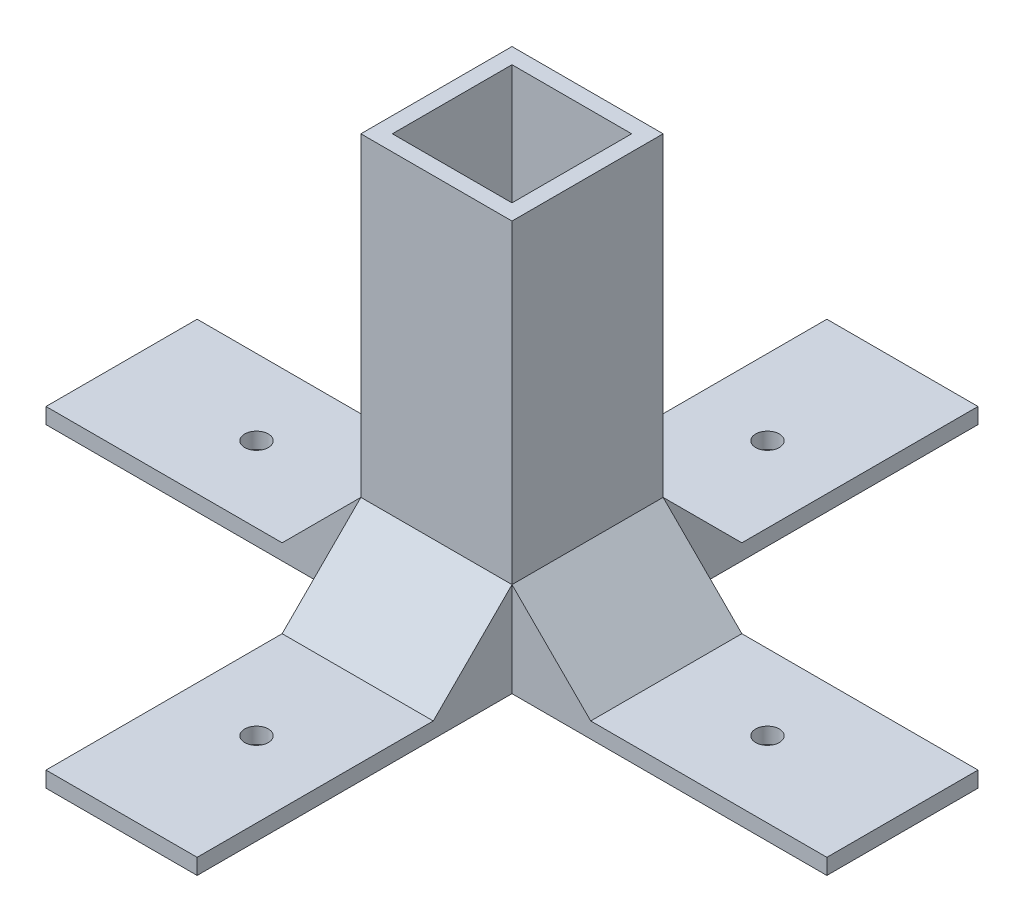
SolidWorks part; units mm, degrees
material "ABS"
ref_plane "Front Plane" through (0, 0, 0) normal (0, 0, 1) x (1, 0, 0)
ref_plane "Top Plane" through (0, 0, 0) normal (0, 1, 0) x (1, 0, 0)
ref_plane "Right Plane" through (0, 0, 0) normal (1, 0, 0) x (0, 0, -1)
sketch "Sketch1" plane through (0, 0, 0) normal (0, 1, 0) x (1, 0, 0)
  line L1 (-7.6, 7.6) -> (7.6, 7.6)
  line L2 (-7.6, 7.6) -> (-7.6, -7.6)
  line L3 (-7.6, -7.6) -> (7.6, -7.6)
  line L4 (7.6, 7.6) -> (7.6, -7.6)
  line L5 (-7.6, 7.6) -> (7.6, -7.6) construction
  line L6 (-7.6, -7.6) -> (7.6, 7.6) construction
  point P0 (0, 0)
  dimension "D1" = 15.2
  dimension "D2" = 15.2
extrude "Extrude-Thin1" add sketch "Sketch1" along normal blind 50 thin thin type one direction wall 2
sketch "Sketch2" plane through (0, 0, 0) normal (0, 1, 0) x (1, 0, 0)
  line L0 (9.6, 9.6) -> (49.6, 9.6)
  line L1 (9.6, -9.6) -> (49.6, -9.6)
  line L2 (49.6, -9.6) -> (49.6, 9.6)
  line L3 (9.6, -9.6) -> (9.6, -49.6)
  line L4 (-9.6, -49.6) -> (9.6, -49.6)
  line L5 (-9.6, -9.6) -> (-9.6, -49.6)
  line L6 (-9.6, -9.6) -> (-49.6, -9.6)
  line L7 (-49.6, 9.6) -> (-49.6, -9.6)
  line L8 (-9.6, 9.6) -> (-49.6, 9.6)
  line L9 (-9.6, 9.6) -> (-9.6, 49.6)
  line L10 (9.6, 49.6) -> (-9.6, 49.6)
  line L11 (9.6, 9.6) -> (9.6, 49.6)
  point P21 (0, 0)
  dimension "D1" = 40
  dimension "D2" = 4
extrude "Boss-Extrude1" add sketch "Sketch2" against normal blind 2
chamfer "Chamfer1" distance 10 angle 45 1 edges at (-9.6, 0, 0)
sketch "Sketch5" plane through (0, 0, 0) normal (0, 1, 0) x (1, 0, 0)
  circle A0 centre (0, 0) radius 53.2121 construction
chamfer "Chamfer2" distance 10 angle 45 1 edges at (0, 0, -9.6)
chamfer "Chamfer3" distance 10 angle 45 1 edges at (9.6, 0, 0)
chamfer "Chamfer4" distance 10 angle 45 1 edges at (0, 0, 9.6)
sketch "Sketch6" plane through (0, 0, 0) normal (0, 1, 0) x (1, 0, 0)
  circle A0 centre (0, 32.4554) radius 1.5
  circle A1 centre (32.4554, 0) radius 1.5
  circle A2 centre (0, -32.4554) radius 1.5
  circle A3 centre (-32.4554, 0) radius 1.5
  point P11 (0, 0)
  dimension "D1" = 3
  dimension "D2" = 4
extrude "Cut-Extrude1" cut sketch "Sketch6" against normal through all
